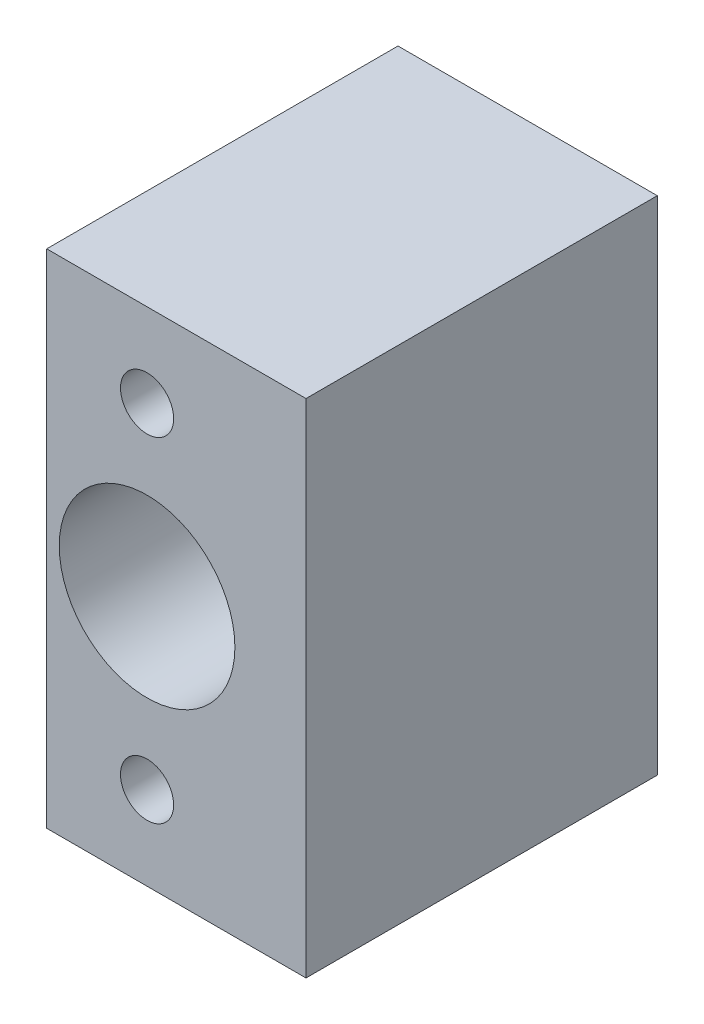
SolidWorks part; units mm, degrees
material "6061-T4 (SS)"
ref_plane "Front Plane" through (0, 0, 0) normal (0, 0, 1) x (1, 0, 0)
ref_plane "Top Plane" through (0, 0, 0) normal (0, 1, 0) x (1, 0, 0)
ref_plane "Right Plane" through (0, 0, 0) normal (1, 0, 0) x (0, 0, -1)
sketch "Sketch1" plane through (0, 0, 0) normal (0, 0, 1) x (1, 0, 0)
  line L5 (-6, 6) -> (0, 0) construction
  line L6 (0, 0) -> (6, 6) construction
  line L7 (9.5, 15) -> (-9.5, 15)
  line L8 (9.5, 15) -> (9.5, -15)
  line L9 (9.5, -15) -> (-9.5, -15)
  line L10 (-9.5, 15) -> (-9.5, -15)
  line L11 (9.5, 15) -> (-9.5, -15) construction
  line L12 (9.5, -15) -> (-9.5, 15) construction
  point P0 (0, 0)
  dimension "D1" = 19
  dimension "D4" = 30
extrude "Boss-Extrude1" add sketch "Sketch1" along normal blind 18
sketch "Sketch2" plane through (0, 0, 18) normal (0, 0, 1) x (1, 0, 0)
  circle A0 centre (0, 0) radius 5.25
  dimension "D1" = 10.5
extrude "Cut-Extrude1" cut sketch "Sketch2" against normal blind 11.5 contours A0
sketch "Sketch4" plane through (0, 0, 6.5) normal (0, 0, 1) x (1, 0, 0)
  circle A0 centre (0, 0) radius 4.8
  dimension "D1" = 9.6
extrude "Cut-Extrude3" cut sketch "Sketch4" against normal blind 1
sketch "Sketch5" plane through (0, 0, 5.5) normal (0, 0, 1) x (1, 0, 0)
  circle A0 centre (0, 0) radius 2.36
  dimension "D1" = 4.72
extrude "Cut-Extrude4" cut sketch "Sketch5" against normal blind 5 and the other way through all
sketch "Sketch6" plane through (0, 0, 0) normal (0, 0, 1) x (1, 0, 0)
  line L0 (-6, 15) -> (-6, -15)
  line L3 (9.5, 15) -> (-9.5, 15) construction
  line L4 (-9.5, -15) -> (9.5, -15) construction
  circle A0 centre (0, 0) radius 5.25 construction
  point P6 (-6, 0)
  dimension "D1" = 6
extrude "Cut-Extrude6" cut sketch "Sketch6" against normal through all and the other way through all flip side to cut
sketch "Sketch11" plane through (0, 0, 0) normal (0, 0, -1) x (-1, 0, 0)
  line L1 (6, 15) -> (-9.5, 15)
  line L2 (6, 15) -> (6, -15)
  line L3 (6, -15) -> (-9.5, -15)
  line L4 (-9.5, 15) -> (-9.5, -15)
extrude "Boss-Extrude5" add sketch "Sketch11" along normal blind 5
sketch "Sketch12" plane through (0, 0, -5) normal (0, 0, -1) x (-1, 0, 0)
  circle A0 centre (0, 0) radius 4
  dimension "D1" = 8
extrude "Cut-Extrude8" cut sketch "Sketch12" against normal blind 5
sketch "Sketch13" plane through (0, 0, -5) normal (0, 0, -1) x (-1, 0, 0)
  line L2 (6, 15) -> (-9.5, 15) construction
  line L3 (0, 15) -> (0, -15) construction
  line L4 (-9.5, -15) -> (6, -15) construction
  circle A1 centre (0, -10) radius 1.5875
  circle A2 centre (0, 10) radius 1.5875
  point P0 (0, 5)
  point P4 (0, -5)
  point P6 (0, 0)
  dimension "D3" = 3.175
  dimension "D4" = 10
  dimension "D1" = 5
  dimension "D2" = 5
extrude "Cut-Extrude9" cut sketch "Sketch13" against normal through all
sketch "Sketch14" plane through (0, 0, 5.5) normal (0, 0, 1) x (1, 0, 0)
  circle A0 centre (0, 0) radius 3
  dimension "D1" = 6
extrude "Cut-Extrude10" cut sketch "Sketch14" against normal blind 1
sketch "Sketch15" plane through (0, -15, 0) normal (0, -1, 0) x (1, 0, 0)
  line L1 (-6, -5) -> (9.5, -5) construction
  line L2 (-6, -5) -> (-6, 16) construction
  line L3 (-6, 16) -> (9.5, 16)
  line L4 (9.5, -5) -> (9.5, 16) construction
  line L5 (9.5, 18) -> (9.5, -5) construction
  line L6 (-6, 16) -> (9.5, 16)
  line L7 (-6, 16) -> (-6, 17) construction
  line L8 (-6, 17) -> (9.5, 17) construction
  line L9 (9.5, 16) -> (9.5, 17) construction
  line L11 (-6, 18) -> (9.5, 18)
  line L12 (-6, 18) -> (-6, 16)
  line L13 (-6, 16) -> (9.5, 16)
  line L14 (9.5, 18) -> (9.5, 16)
  line M5 (9.5, 18) -> (-6, 18)
  line M6 (-6, 18) -> (-6, -5)
  line M8 (9.5, -5) -> (9.5, 18)
  dimension "D1" = 21
  dimension "D2" = 1
extrude "Cut-Extrude11" cut sketch "Sketch15" against normal blind 41 contours L3 M6 M8 M5 region at (1.75, -15, 17)
